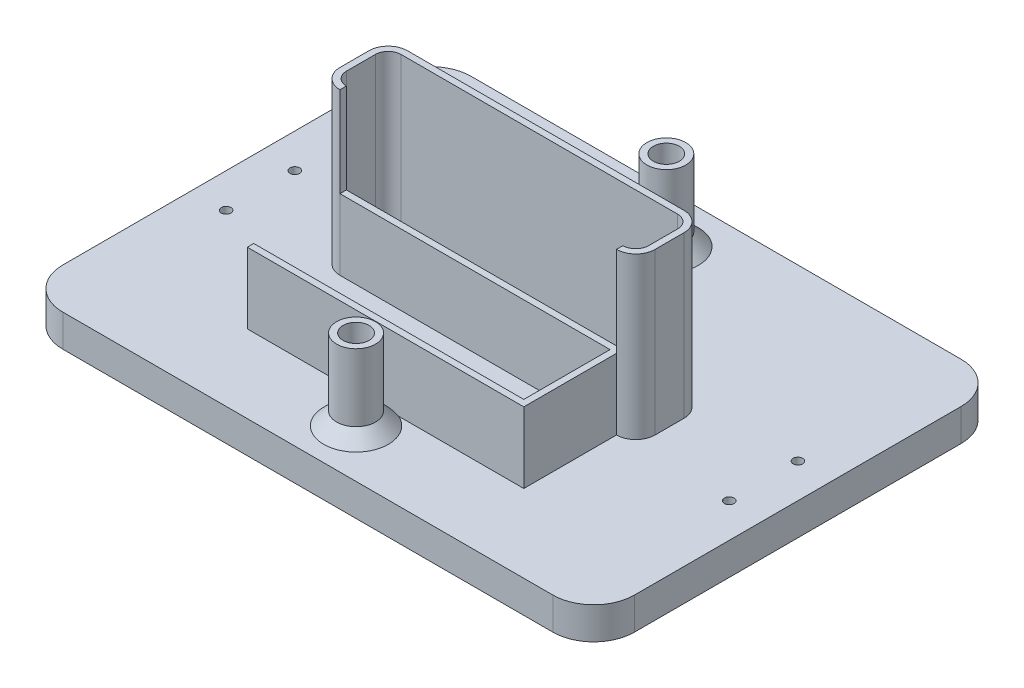
SolidWorks part; units mm, degrees
ref_plane "Front Plane" through (0, 0, 0) normal (0, 0, 1) x (1, 0, 0)
ref_plane "Top Plane" through (0, 0, 0) normal (0, 1, 0) x (1, 0, 0)
ref_plane "Right Plane" through (0, 0, 0) normal (1, 0, 0) x (0, 0, -1)
sketch "Sketch2" plane through (0, 0, 0) normal (0, 1, 0) x (1, 0, 0)
  line L1 (-76.2, 63.5) -> (76.2, 63.5)
  line L2 (-88.9, 50.8) -> (-88.9, -50.8)
  line L3 (-76.2, -63.5) -> (76.2, -63.5)
  line L4 (88.9, 50.8) -> (88.9, -50.8)
  line L5 (-88.9, 63.5) -> (88.9, -63.5) construction
  line L6 (-88.9, -63.5) -> (88.9, 63.5) construction
  arc A0 (-88.9, -50.8) -> (-76.2, -63.5) centre (-76.2, -50.8) ccw
  arc A1 (76.2, -63.5) -> (88.9, -50.8) centre (76.2, -50.8) ccw
  arc A2 (76.2, 63.5) -> (88.9, 50.8) centre (76.2, 50.8) cw
  arc A3 (-76.2, 63.5) -> (-88.9, 50.8) centre (-76.2, 50.8) ccw
  point P0 (0, 0)
  dimension "D3" = 12.7
  dimension "D1" = 177.8
  dimension "D2" = 127
extrude "Boss-Extrude1" add sketch "Sketch2" along normal blind 10
sketch "Sketch3" plane through (0, 10, 0) normal (0, 1, 0) x (1, 0, 0)
  line L0 (0, 66.5941) -> (0, -70.2646) construction
  line L1 (76.2, 63.5) -> (-76.2, 63.5) construction
  line L2 (-76.2, -63.5) -> (76.2, -63.5) construction
  circle A0 centre (0, -48.5) radius 4.05
  circle A1 centre (0, 48) radius 4.05
  circle A2 centre (0, 48) radius 6.05
  circle A3 centre (0, -48.5) radius 6.05
  dimension "D3" = 8.1
  dimension "D4" = 8.1
  dimension "D1" = 15.5
  dimension "D2" = 15
  dimension "D5" = 2
extrude "Boss-Extrude2" add sketch "Sketch3" along normal blind 25
sketch "Sketch4" plane through (0, 10, 0) normal (0, 1, 0) x (1, 0, 0)
  line L0 (-88.9, 50.8) -> (-88.9, -50.8) construction
  line L1 (76.2, 63.5) -> (-76.2, 63.5) construction
  line L2 (0, -19.25) -> (0, 19.25) construction
  circle A0 centre (-78.23, 10.69) radius 1.5
  circle A1 centre (-78.23, -10.69) radius 1.5
  circle A2 centre (78.23, -10.69) radius 1.5
  circle A3 centre (78.23, 10.69) radius 1.5
  dimension "D1" = 3
  dimension "D2" = 3
  dimension "D3" = 10.67
  dimension "D4" = 21.38
  dimension "D5" = 52.81
extrude "Cut-Extrude1" cut sketch "Sketch4" against normal through all
sketch "Sketch5" plane through (0, 0, 0) normal (0, -1, 0) x (1, 0, 0)
  circle A5 centre (-78.23, 10.69) radius 3
  circle A6 centre (-78.23, 10.69) radius 3
  circle A8 centre (-78.23, -10.69) radius 3
  circle A9 centre (-78.23, -10.69) radius 3
  circle A11 centre (78.23, 10.69) radius 3
  circle A12 centre (78.23, 10.69) radius 3
  circle A14 centre (78.23, -10.69) radius 3
  circle A15 centre (78.23, -10.69) radius 3
  dimension "D1" = 1.5
  dimension "D2" = 1.5
  dimension "D3" = 1.5
  dimension "D4" = 1.5
extrude "Cut-Extrude2" cut sketch "Sketch5" against normal blind 4
sketch "Sketch6" plane through (0, 10, 0) normal (0, 1, 0) x (1, 0, 0)
  line L1 (-43, 8.5) -> (43, 8.5)
  line L2 (-47, 4.5) -> (-47, -4.5)
  line L3 (-43, -8.5) -> (43, -8.5)
  line L4 (47, 4.5) -> (47, -4.5)
  line L5 (-47, 8.5) -> (47, -8.5) construction
  line L6 (-47, -8.5) -> (47, 8.5) construction
  arc A0 (43, 8.5) -> (47, 4.5) centre (43, 4.5) cw
  arc A1 (43, -8.5) -> (47, -4.5) centre (43, -4.5) ccw
  arc A2 (-47, -4.5) -> (-43, -8.5) centre (-43, -4.5) ccw
  arc A3 (-43, 8.5) -> (-47, 4.5) centre (-43, 4.5) ccw
  point P0 (0, 0)
  dimension "D3" = 4
  dimension "D1" = 17
  dimension "D2" = 94
extrude "Cut-Extrude3" cut sketch "Sketch6" against normal through all
sketch "Sketch7" plane through (0, 10, 0) normal (0, 1, 0) x (1, 0, 0)
  line L0 (40.9977, -37.3272) -> (-41, -37.3272)
  line L1 (42.9977, -39.3272) -> (-43, -39.3272)
  line L2 (42.9977, -39.3272) -> (42.9977, -8.5)
  line L3 (42.9977, -8.5) -> (-43, -8.5)
  line L4 (-43, -39.3272) -> (-43, -8.5)
  line L5 (-41, -37.3272) -> (-41, -10.5)
  line L6 (40.9977, -10.5) -> (-41, -10.5)
  line L7 (40.9977, -37.3272) -> (40.9977, -10.5)
  dimension "D1" = 2
extrude "Boss-Extrude3" add sketch "Sketch7" along normal blind 22
sketch "Sketch8" plane through (0, 10, 0) normal (0, 1, 0) x (1, 0, 0)
  line L2 (-41, -37.3272) -> (-112.2496, -37.3272)
  line L5 (-41, -37.3272) -> (40.9977, -37.3272)
  line L6 (40.9977, -37.3272) -> (40.9977, -10.5)
  line L7 (40.9977, -10.5) -> (-41, -10.5)
  line L8 (-41, -10.5) -> (-41, -37.3272)
  line L10 (-41, -37.3272) -> (40.9977, -37.3272)
  line L11 (40.9977, -37.3272) -> (40.9977, -10.5)
  line L12 (40.9977, -10.5) -> (-41, -10.5)
  line L13 (-41, -10.5) -> (-41, -37.3272)
  dimension "D1" = 0
sketch "Sketch9" plane through (-43, 0, 0) normal (-1, 0, 0) x (0, 0, 1)
  line L0 (10.5, 10) -> (37.3272, 10) construction
  line L1 (10.5, 32) -> (37.3272, 32)
  line L2 (10.5, 32) -> (10.5, 10)
  line L3 (10.5, 10) -> (37.3272, 10)
  line L4 (37.3272, 32) -> (37.3272, 10)
  line L5 (37.3272, 10) -> (10.5, 10) construction
extrude "Cut-Extrude7" cut sketch "Sketch9" against normal blind 22
sketch "Sketch10" plane through (0, 10, 0) normal (0, 1, 0) x (1, 0, 0)
  line L11 (47, -4.5) -> (47, 4.5) construction
  line L12 (-47, 4.5) -> (-47, -4.5) construction
  line L13 (43, 8.5) -> (-43, 8.5) construction
  line L14 (-49, 4.5) -> (-49, -4.5)
  line L15 (49, -4.5) -> (49, 4.5)
  line L16 (43, 10.5) -> (-43, 10.5)
  line L17 (-49, 4.5) -> (-49, -4.5)
  line L18 (49, -4.5) -> (49, 4.5)
  line L19 (43, 10.5) -> (-43, 10.5)
  line L20 (47, -4.5) -> (47, 4.5)
  line L21 (-47, 4.5) -> (-47, -4.5)
  line L22 (43, 8.5) -> (-43, 8.5)
  line L23 (-43, -8.5) -> (-43, -10.5)
  line L24 (43, -8.5) -> (43, -10.5)
  arc A17 (47, 4.5) -> (43, 8.5) centre (43, 4.5) ccw construction
  arc A18 (43, -8.5) -> (47, -4.5) centre (43, -4.5) ccw construction
  arc A19 (-47, -4.5) -> (-43, -8.5) centre (-43, -4.5) ccw construction
  arc A20 (-43, 8.5) -> (-47, 4.5) centre (-43, 4.5) ccw construction
  arc A21 (-49, -4.5) -> (-43, -10.5) centre (-43, -4.5) ccw
  arc A22 (43, -10.5) -> (49, -4.5) centre (43, -4.5) ccw
  arc A23 (49, 4.5) -> (43, 10.5) centre (43, 4.5) ccw
  arc A24 (-43, 10.5) -> (-49, 4.5) centre (-43, 4.5) ccw
  arc A25 (-49, -4.5) -> (-43, -10.5) centre (-43, -4.5) ccw
  arc A26 (43, -10.5) -> (49, -4.5) centre (43, -4.5) ccw
  arc A27 (49, 4.5) -> (43, 10.5) centre (43, 4.5) ccw
  arc A28 (-43, 10.5) -> (-49, 4.5) centre (-43, 4.5) ccw
  arc A29 (47, 4.5) -> (43, 8.5) centre (43, 4.5) ccw
  arc A30 (43, -8.5) -> (47, -4.5) centre (43, -4.5) ccw
  arc A31 (-47, -4.5) -> (-43, -8.5) centre (-43, -4.5) ccw
  arc A32 (-43, 8.5) -> (-47, 4.5) centre (-43, 4.5) ccw
  point P7 (42.9977, -10.2077)
  dimension "D1" = 2
extrude "Boss-Extrude4" add sketch "Sketch10" along normal blind 50
sketch "Sketch11" plane through (0, 0, 0) normal (0, -1, 0) x (1, 0, 0)
  line L0 (-17.3024, 23.3335) -> (17.3024, 23.3335) construction
  line L1 (-17.3024, 25.9042) -> (17.3024, 25.9042)
  line L2 (-17.3024, 20.7629) -> (17.3024, 20.7629)
  arc A0 (-17.3024, 25.9042) -> (-17.3024, 20.7629) centre (-17.3024, 23.3335) ccw
  arc A1 (17.3024, 20.7629) -> (17.3024, 25.9042) centre (17.3024, 23.3335) ccw
  point P2 (0, 23.3335)
extrude "Cut-Extrude8" cut sketch "Sketch11" against normal blind 22
chamfer "Chamfer2" distance 4 angle 45 2 edges at (0, 10, 54.55) (0, 10, -41.95)
